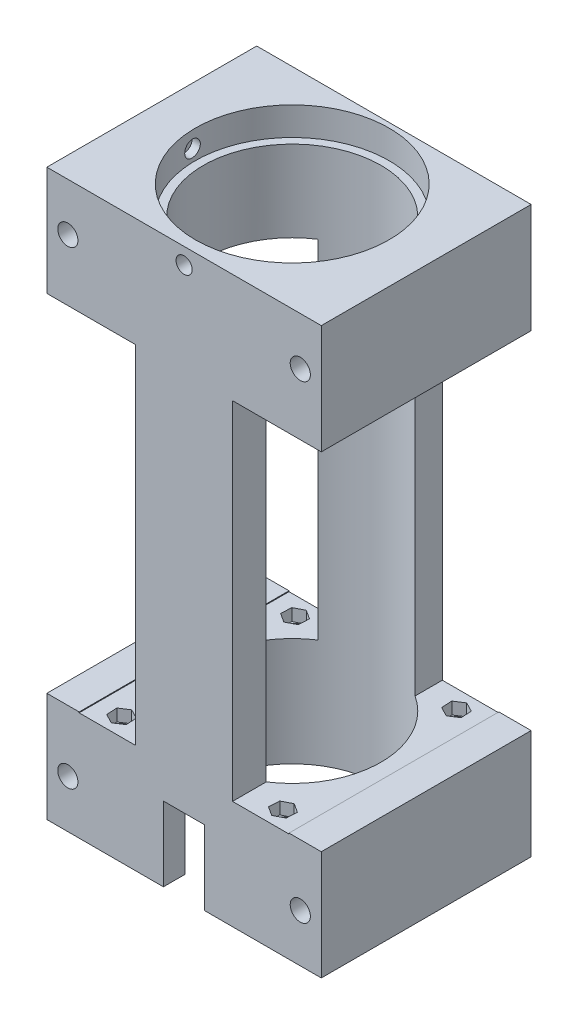
SolidWorks part; units mm, degrees
ref_plane "Front" through (0, 0, 0) normal (0, 0, 1) x (1, 0, 0)
ref_plane "Top" through (0, 0, 0) normal (0, 1, 0) x (1, 0, 0)
ref_plane "Right" through (0, 0, 0) normal (1, 0, 0) x (0, 0, -1)
sketch "草图1" plane through (0, 0, 0) normal (0, 0, 1) x (1, 0, 0)
  line L0 (-100, -70) -> (100, -70) construction
  line L1 (26, 70) -> (-26, 70)
  line L2 (26, 70) -> (26, -70)
  line L3 (26, -70) -> (-26, -70)
  line L4 (-26, 70) -> (-26, -70)
  line L5 (26, 70) -> (-26, -70) construction
  line L6 (26, -70) -> (-26, 70) construction
  point P0 (0, 0)
  dimension "D1" = 52
extrude "凸台-拉伸1" add sketch "草图1" along normal blind 52
sketch "草图2" plane through (0, 70, 0) normal (0, 1, 0) x (1, 0, 0)
  line L0 (26, 0) -> (-26, 0) construction
  circle A0 centre (0, -25.2) radius 22
  dimension "D1" = 44
  dimension "D2" = 25.2
extrude "切除-拉伸1" cut sketch "草图2" against normal through all contours A0
sketch "草图3" plane through (0, 0, 52) normal (0, 0, 1) x (1, 0, 0)
  line L1 (26, -70) -> (26, 70) construction
  line L3 (26, -43.1) -> (26, 42.9)
  line L4 (26, -43.1) -> (12, -43.1)
  line L5 (12, -43.1) -> (12, 42.9)
  line L6 (12, 42.9) -> (26, 42.9)
  line L7 (-26, -70) -> (26, -70) construction
  point P0 (19, -43.1)
  dimension "D1" = 86
  dimension "D2" = 26.9
  dimension "D3" = 14
extrude "切除-拉伸2" cut sketch "草图3" against normal up to surface (52 mm away)
mirror "镜向1" about plane through (0, 0, 0) normal (1, 0, 0) of "切除-拉伸2"
sketch "草图4" plane through (0, 70, 0) normal (0, 1, 0) x (1, 0, 0)
  circle A0 centre (0, -25.2) radius 24
  dimension "D1" = 48
extrude "切除-拉伸3" cut sketch "草图4" against normal blind 7
sketch "草图5" plane through (26, 0, 0) normal (1, 0, 0) x (0, 0, -1)
  line L0 (-52, 70) -> (0, 70) construction
  circle A0 centre (-26, 66) radius 2
  point P5 (-26, 70)
  dimension "D1" = 4
  dimension "D2" = 4
extrude "切除-拉伸4" cut sketch "草图5" against normal through all
sketch "草图6" plane through (0, 0, 52) normal (0, 0, 1) x (1, 0, 0)
  line L0 (26, 70) -> (-26, 70) construction
  circle A0 centre (0, 66) radius 2
  dimension "D1" = 4
  dimension "D2" = 4
extrude "切除-拉伸5" cut sketch "草图6" against normal blind 20
sketch "草图7" plane through (0, -43.1, 0) normal (0, 1, 0) x (1, 0, 0)
  line L0 (-12, -52) -> (-26, -52) construction
  line L1 (-22.3629, -46.2876) -> (-22.2314, -48.9402)
  line L2 (-22.2314, -48.9402) -> (-19.8685, -50.1526)
  line L3 (-19.8685, -50.1526) -> (-17.6371, -48.7124)
  line L4 (-17.6371, -48.7124) -> (-17.7686, -46.0598)
  line L5 (-17.7686, -46.0598) -> (-20.1315, -44.8474)
  line L6 (-20.1315, -44.8474) -> (-22.3629, -46.2876)
  line L7 (-26, 0) -> (-26, -52) construction
  circle A0 centre (-20, -47.5) radius 2.3 construction
  dimension "D1" = 4.6
  dimension "D2" = 4.5
  dimension "D3" = 6
extrude "切除-拉伸6" cut sketch "草图7" against normal blind 3
sketch "草图8" plane through (0, -46.1, 0) normal (0, 1, 0) x (1, 0, 0)
  line L0 (-26, 0) -> (-26, -52) construction
  line L1 (-12, -52) -> (-26, -52) construction
  circle A0 centre (-20, -47.5) radius 2.05
  dimension "D1" = 4.1
  dimension "D2" = 6
  dimension "D3" = 4.5
extrude "切除-拉伸7" cut sketch "草图8" against normal through all
mirror "镜向2" about plane through (0, 0, 0) normal (1, 0, 0) of "切除-拉伸6", "切除-拉伸7"
ref_plane "基准面2" through (0, 0, 26) normal (0, 0, 1) x (1, 0, 0)
mirror "镜向3" about plane through (0, 0, 26) normal (0, 0, 1) of "镜向2"
sketch "草图9" plane through (0, 0, 52) normal (0, 0, 1) x (1, 0, 0)
  line L0 (-26, 70) -> (-26, 42.9) construction
  line L1 (26, 42.9) -> (26, 70) construction
  line L2 (-26, 70) -> (-26, 42.9)
  line L3 (26, 42.9) -> (26, 70)
  line L4 (26, 42.9) -> (34, 42.9)
  line L5 (34, 42.9) -> (34, 70)
  line L6 (34, 70) -> (26, 70)
  line L7 (-26, 42.9) -> (-34, 42.9)
  line L8 (-34, 42.9) -> (-34, 70)
  line L9 (-34, 70) -> (-26, 70)
  dimension "D1" = 8
extrude "凸台-拉伸2" add sketch "草图9" against normal up to surface (52 mm away)
sketch "草图10" plane through (0, 0, 52) normal (0, 0, 1) x (1, 0, 0)
  line L0 (-34, 70) -> (-34, 42.9) construction
  line L1 (34, 42.9) -> (34, 70) construction
  circle A0 centre (28.8, 58.1086) radius 2.5
  circle A1 centre (-28.8, 58.1086) radius 2.5
  dimension "D1" = 5
  dimension "D2" = 5
  dimension "D3" = 5.2
  dimension "D4" = 5.2
extrude "切除-拉伸8" cut sketch "草图10" against normal through all
ref_plane "基准面3" through (0, 0, 0) normal (0, 1, 0) x (1, 0, 0)
mirror "镜向4" about plane through (0, 0, 0) normal (0, 1, 0) of "切除-拉伸8", "凸台-拉伸2"
sketch "草图11" plane through (0, 0, 52) normal (0, 0, 1) x (1, 0, 0)
  line L0 (-34, -70) -> (34, -70) construction
  line L1 (-5.1222, -70) -> (5, -70)
  line L2 (5, -70) -> (5, -51.5841)
  line L3 (5, -51.5841) -> (-5.1222, -51.5841)
  line L4 (-5.1222, -51.5841) -> (-5.1222, -70)
extrude "切除-拉伸9" cut sketch "草图11" against normal blind 10
